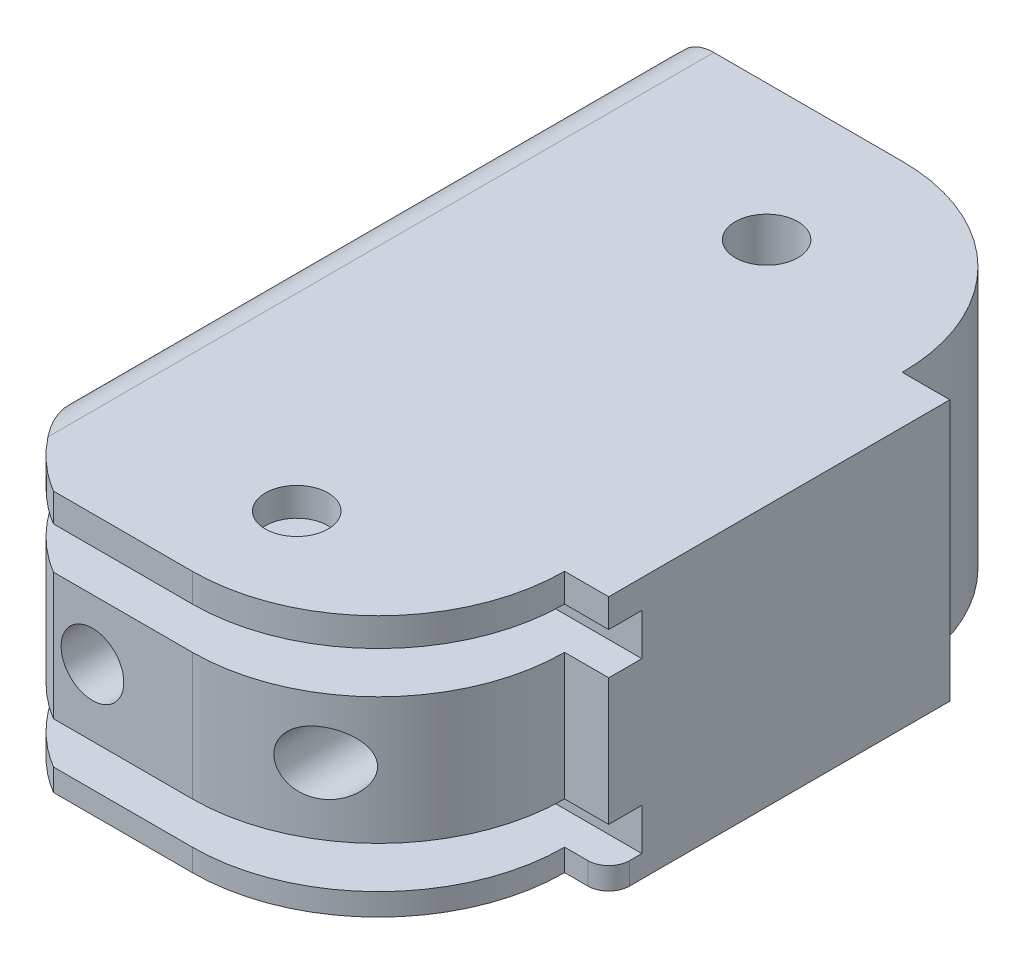
SolidWorks part; units mm, degrees
ref_plane "Front Plane" through (0, 0, 0) normal (0, 0, 1) x (1, 0, 0)
ref_plane "Top Plane" through (0, 0, 0) normal (0, 1, 0) x (1, 0, 0)
ref_plane "Right Plane" through (0, 0, 0) normal (1, 0, 0) x (0, 0, -1)
sketch "Sketch1" plane through (0, 0, 0) normal (0, 0, 1) x (1, 0, 0)
  line L0 (-24.2561, -24.0702) -> (-22.0061, -24.0702) construction
  line L1 (-24.2561, -17.8202) -> (-2.2017, -17.8202)
  line L2 (-24.2561, -17.8202) -> (-24.2561, -30.3202)
  line L3 (-24.2561, -30.3202) -> (-2.2017, -30.3202)
  line L4 (-2.2017, -17.8202) -> (-2.2017, -30.3202)
  line L5 (-2.2017, -24.0702) -> (-4.4517, -24.0702) construction
  line L6 (-22.0061, -24.0702) -> (-22.0061, -30.3202) construction
  line L7 (-4.4517, -24.0702) -> (-4.4517, -30.3202) construction
extrude "Boss-Extrude1" add sketch "Sketch1" along normal blind 34
sketch "Sketch2" plane through (0, -30.3202, 0) normal (0, -1, 0) x (1, 0, 0)
  line L0 (-4.3151, 25.0862) -> (-2.2017, 25.0862)
  line L1 (-24.2561, 0) -> (-2.2017, 0) construction
  line L2 (-13.2289, 0) -> (-13.2289, 8.75) construction
  line L4 (-24.2561, 34) -> (-24.2561, 0) construction
  line L5 (-4.4789, 8.75) -> (-2.2017, 8.75)
  line L6 (-2.2017, 34) -> (-2.2017, 0) construction
  line L7 (-13.2289, 34) -> (-13.2289, 29) construction
  line L8 (-24.2561, 34) -> (-2.2017, 34) construction
  line L11 (-13.2289, 8.75) -> (-13.2289, 6.5) construction
  line L12 (-24.2561, 0) -> (-2.2017, 0) construction
  arc A1 (-13.2289, 0) -> (-4.4789, 8.75) centre (-13.2289, 8.75) ccw
  circle A4 centre (-13.2289, 6.5) radius 1.5
  arc A6 (-4.3151, 25.0862) -> (-13.2289, 34) centre (-13.2289, 25.0862) ccw
  circle A8 centre (-13.2289, 29) radius 1.5
  spline S0 degree 3 poles (-2.2017, 8.75) (5.3921, 3.8803) (-0.7771, -4.5233) (-17.1743, -10.6233) (-34.8214, -0.026) (-24.2561, 8.75) knots 0 0 0 0 0.283273 0.504245 1 1 1 1
  spline S1 degree 3 poles (-24.2561, 25.4586) (-35.656, 36.5403) (-13.0069, 52.2851) (9.3223, 36.3385) (-2.2017, 25.0862) knots 0 0 0 0 0.496842 1 1 1 1
  spline S2 degree 1 poles (-13.2289, 0) (-23.4906, 0) knots 0 0 1 1
  spline S3 degree 2 poles (-23.4906, 0) (-24.9665, 4.2378) (-24.2561, 8.75) knots 0 0 0 1 1 1
  spline S4 degree 3 poles (-13.2289, 34) (-19.0864, 37.4223) (-24.8857, 30.869) (-24.2561, 25.4586) knots 0 0 0 0 1 1 1 1
extrude "Cut-Extrude1" cut sketch "Sketch2" against normal blind 15 and the other way blind 10
fillet "Fillet3" radius 2 4 edges at (-24.2561, -17.8202, 15.0641) (-24.2561, -30.3202, 15.0641) (-24.2561, -24.0702, 3.0015) (-24.2561, -24.0702, 27.1267)
ref_plane "Plane1" through (0, 0, 0) normal (0, 0, 1) x (1, 0, 0)
sketch "Sketch5" plane through (0, 0, 0) normal (0, 0, 1) x (1, 0, 0)
  line L0 (-2.2017, -24.0702) -> (-8.4468, -24.0702) construction
  line L1 (-2.2017, -30.3202) -> (-24.2561, -30.3202) construction
  line L2 (-2.2017, -30.3202) -> (-2.2017, -17.8202) construction
  line L3 (-2.2017, -17.8202) -> (-24.2561, -17.8202) construction
  line L4 (-24.2561, -30.3202) -> (-24.2561, -17.8202) construction
  line L5 (-24.2561, -24.0702) -> (-18.0111, -24.0702) construction
  circle A0 centre (-18.0111, -24.0702) radius 1.5
  circle A1 centre (-8.4468, -24.0702) radius 1.5
extrude "Cut-Extrude4" cut sketch "Sketch5" along normal through all
ref_plane "Plane5" through (0, 0, 38) normal (0, 0, 1) x (1, 0, 0)
sketch "Sketch16" plane through (0, 0, 38) normal (0, 0, 1) x (1, 0, 0)
  line L0 (-2.2017, -17.681) -> (-2.2017, -19.181) construction
  line L1 (-2.2017, -17.681) -> (-24.2561, -17.681) construction
  line L2 (-2.2017, -17.681) -> (-2.2017, -30.7619) construction
  line L3 (-2.2017, -30.7619) -> (-24.2561, -30.7619) construction
  line L4 (-24.2561, -17.681) -> (-24.2561, -30.7619) construction
  line L5 (-2.2017, -17.681) -> (-24.2561, -30.7619) construction
  line L6 (-2.2017, -30.7619) -> (-24.2561, -17.681) construction
  line L7 (-2.2017, -30.7619) -> (-2.2017, -29.2619) construction
  line L9 (-2.2017, -19.181) -> (-24.2561, -19.181)
  line L10 (-2.2017, -19.181) -> (-2.2017, -21.181)
  line L11 (-2.2017, -21.181) -> (-24.2561, -21.181)
  line L12 (-24.2561, -19.181) -> (-24.2561, -21.181)
  line L13 (-2.2017, -19.181) -> (-24.2561, -21.181) construction
  line L14 (-2.2017, -21.181) -> (-24.2561, -19.181) construction
  line L15 (-2.2017, -29.2619) -> (-24.2561, -29.2619)
  line L16 (-2.2017, -29.2619) -> (-2.2017, -27.2619)
  line L17 (-2.2017, -27.2619) -> (-24.2561, -27.2619)
  line L18 (-24.2561, -29.2619) -> (-24.2561, -27.2619)
  line L19 (-2.2017, -29.2619) -> (-24.2561, -27.2619) construction
  line L20 (-2.2017, -27.2619) -> (-24.2561, -29.2619) construction
  point P4 (-13.2289, -24.2214)
  point P10 (-13.2289, -20.181)
  point P14 (-13.2289, -28.2619)
extrude "Cut-Extrude6" cut sketch "Sketch16" against normal blind 14.5
fillet "Fillet4" radius 1 1 edges at (-2.2017, -29.7911, 25.0862)
